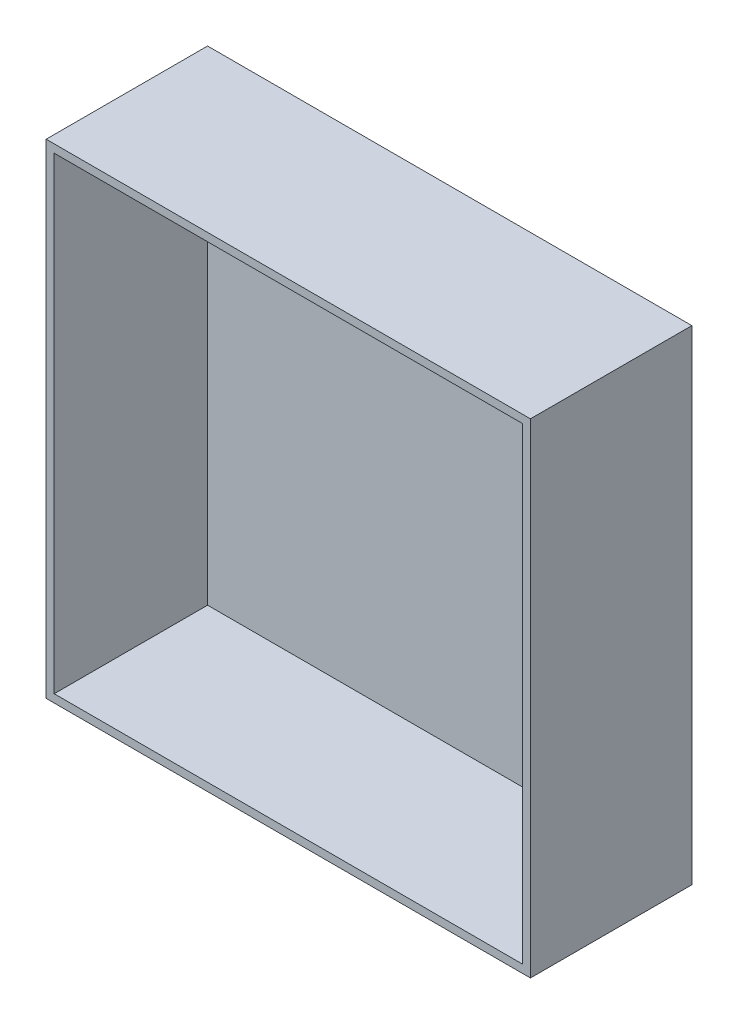
SolidWorks part; units mm, degrees
ref_plane "正面" through (0, 0, 0) normal (0, 0, 1) x (1, 0, 0)
ref_plane "平面" through (0, 0, 0) normal (0, 1, 0) x (1, 0, 0)
ref_plane "右側面" through (0, 0, 0) normal (1, 0, 0) x (0, 0, -1)
sketch "ｽｹｯﾁ1" plane through (0, 0, 0) normal (0, 0, 1) x (1, 0, 0)
  line L1 (0, 0) -> (300, 0)
  line L2 (0, 0) -> (0, -300)
  line L3 (0, -300) -> (300, -300)
  line L4 (300, 0) -> (300, -300)
  dimension "D1" = 300
  dimension "D2" = 300
extrude "ﾎﾞｽ - 押し出し1" add sketch "ｽｹｯﾁ1" along normal blind 100
sketch "ｽｹｯﾁ2" plane through (0, 0, 100) normal (0, 0, 1) x (1, 0, 0)
  line L14 (5, -5) -> (5, -295)
  line L15 (5, -295) -> (295, -295)
  line L16 (295, -295) -> (295, -5)
  line L17 (295, -5) -> (5, -5)
  line L18 (5, -5) -> (5, -295)
  line L19 (5, -295) -> (295, -295)
  line L20 (295, -295) -> (295, -5)
  line L21 (295, -5) -> (5, -5)
  dimension "D1" = 5
extrude "ｶｯﾄ - 押し出し1" cut sketch "ｽｹｯﾁ2" against normal blind 95
